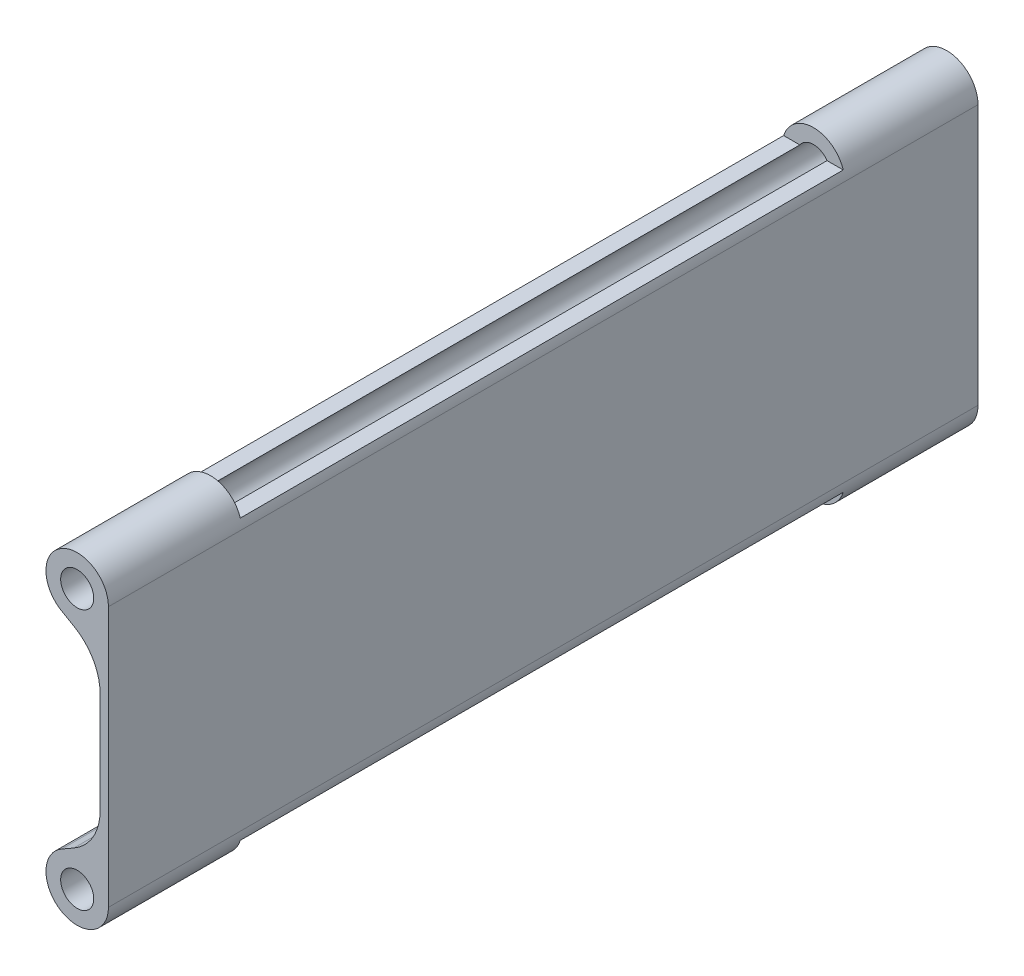
SolidWorks part; units mm, degrees
material "ABS"
ref_plane "Alzado" through (0, 0, 0) normal (0, 0, 1) x (1, 0, 0)
ref_plane "Planta" through (0, 0, 0) normal (0, 1, 0) x (1, 0, 0)
ref_plane "Vista lateral" through (0, 0, 0) normal (1, 0, 0) x (0, 0, -1)
sketch "Croquis1" plane through (0, 0, 0) normal (0, 0, 1) x (1, 0, 0)
  line L5 (-13.465, 0) -> (13.8234, 0) construction
  line L8 (-1.6, 15.5562) -> (-8.9869, 19.7963)
  line L9 (-1.6, 15.5562) -> (-1.6, -15.5562)
  line L10 (0, 25) -> (0, -25)
  line L11 (-1.6, -15.5562) -> (-8.9869, -19.7963)
  circle A0 centre (-6, 25) radius 3.175
  arc A5 (0, 25) -> (-8.9869, 19.7963) centre (-6, 25) ccw
  arc A6 (0, -25) -> (-8.9869, -19.7963) centre (-6, -25) cw
  circle A7 centre (-6, -25) radius 3.175
  point P7 (0, 0)
  point P15 (0, 0)
  point P16 (-1.6, 0)
  point P17 (-1.6, 0)
  dimension "D1" = 6.35
  dimension "D2" = 50
  dimension "D3" = 1.6
  dimension "D4" = 6
extrude "Saliente-Extruir1" add sketch "Croquis1" against normal blind 167
fillet "Redondeo1" radius 10 2 edges at (-1.6, -15.5562, -83.5) (-1.6, 15.5562, -83.5)
sketch "Croquis3" plane through (0, 0, 0) normal (1, 0, 0) x (0, 0, -1)
  line L0 (0, 0) -> (167, 0) construction
  line L1 (25.6041, 44.9478) -> (141.3959, 44.9478)
  line L2 (25.6041, 44.9478) -> (25.6041, 26.8024)
  line L3 (25.6041, 26.8024) -> (141.3959, 26.8024)
  line L4 (141.3959, 44.9478) -> (141.3959, 26.8024)
  line L5 (141.3959, -44.9478) -> (141.3959, -26.8024)
  line L6 (25.6041, -26.8024) -> (141.3959, -26.8024)
  line L7 (25.6041, -44.9478) -> (25.6041, -26.8024)
  line L8 (25.6041, -44.9478) -> (141.3959, -44.9478)
  line L9 (167, 9.7659) -> (167, -9.7659) construction
  point P16 (83.5, 0)
  point P17 (83.5, -26.8024)
extrude "Cortar-Extruir2" cut sketch "Croquis3" against normal through all
